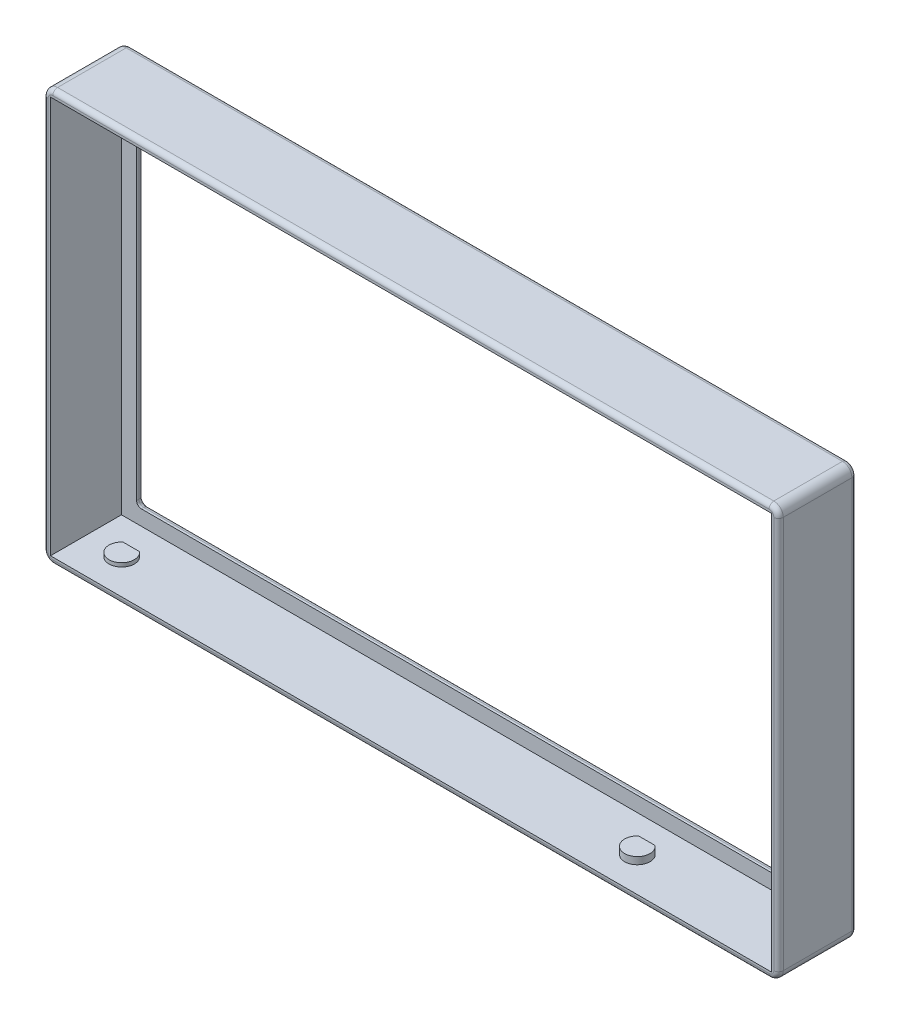
SolidWorks part; units mm, degrees
ref_plane "Front Plane" through (0, 0, 0) normal (0, 0, 1) x (1, 0, 0)
ref_plane "Top Plane" through (0, 0, 0) normal (0, 1, 0) x (1, 0, 0)
ref_plane "Right Plane" through (0, 0, 0) normal (1, 0, 0) x (0, 0, -1)
ref_plane "Plane1" through (0, 0, -28.2226) normal (0, 0, -1) x (-1, 0, 0)
sketch "Sketch1" plane through (0, 0, -28.2226) normal (0, 0, -1) x (-1, 0, 0)
  line L0 (-140.2742, 14.7559) -> (12.1258, 14.7559)
  line L1 (12.1258, 14.7559) -> (12.1258, 98.7359)
  line L2 (12.1258, 98.7359) -> (-140.2742, 98.7359)
  line L3 (-140.2742, 98.7359) -> (-140.2742, 14.7559)
  line L4 (-140.0742, 14.9559) -> (11.9258, 14.9559)
  line L5 (11.9258, 14.9559) -> (11.9258, 98.5359)
  line L6 (11.9258, 98.5359) -> (-140.0742, 98.5359)
  line L7 (-140.0742, 98.5359) -> (-140.0742, 14.9559)
  line L8 (-140.0742, 14.9559) -> (11.9258, 14.9559)
  line L9 (11.9258, 14.9559) -> (11.9258, 98.5359)
  line L10 (11.9258, 98.5359) -> (-140.0742, 98.5359)
  line L11 (-140.0742, 98.5359) -> (-140.0742, 14.9559)
  line L12 (13.6258, 13.2559) -> (13.6258, 100.2359)
  line L13 (13.6258, 100.2359) -> (-141.7742, 100.2359)
  line L14 (-141.7742, 100.2359) -> (-141.7742, 13.2559)
  line L15 (-141.7742, 13.2559) -> (13.6258, 13.2559)
  line L16 (-137.0742, 17.9559) -> (8.9258, 17.9559)
  line L17 (8.9258, 17.9559) -> (8.9258, 95.5359)
  line L18 (8.9258, 95.5359) -> (-137.0742, 95.5359)
  line L19 (-137.0742, 95.5359) -> (-137.0742, 17.9559)
  dimension "D1" = 0
  dimension "D2" = 0.2
  dimension "D3" = 1.5
  dimension "D4" = 3
extrude "Boss-Extrude2" add sketch "Sketch1" along normal blind 1.5 contours L14 L15 L12 L13 L3 L2 L1 L0 | L2 L3 L0 L1 L11 L10 L9 L8 | L10 L11 L8 L9 region at (140.1002, 56.7459, -28.2226) region at (138.3395, 56.7459, -28.2226) region at (64.0742, 13.434, -28.2226)
extrude "Boss-Extrude3" add sketch "Sketch1<4>" against normal blind 15 contours L14 L15 L12 L13 L3 L2 L1 L0 region at (64.0742, 13.434, -28.2226)
sketch "Sketch1<4>" plane through (0, 0, -28.2226) normal (0, 0, -1) x (-1, 0, 0) same geometry as "Sketch1"
fillet "Fillet1" radius 2 4 edges at (141.7742, 100.2359, -21.4726) (-13.6258, 100.2359, -21.4726) (-13.6258, 13.2559, -21.4726) (141.7742, 13.2559, -21.4726)
fillet "Fillet2" radius 1 16 edges at (-8.9258, 56.7459, -29.7226) (64.0742, 95.5359, -29.7226) (64.0742, 17.9559, -29.7226) (141.1884, 99.6501, -29.7226) (64.0742, 100.2359, -29.7226) (-13.04, 99.6501, -29.7226) (-13.6258, 56.7459, -29.7226) (-13.04, 13.8417, -29.7226) (64.0742, 13.2559, -29.7226) (141.1884, 13.8417, -29.7226) (141.7742, 56.7459, -29.7226) (137.0742, 56.7459, -29.7226) (137.0742, 95.5359, -28.9726) (137.0742, 17.9559, -28.9726) (-8.9258, 17.9559, -28.9726) (-8.9258, 95.5359, -28.9726)
fillet "Fillet3" radius 1 8 edges at (141.1884, 13.8417, -13.2226) (141.7742, 56.7459, -13.2226) (141.1884, 99.6501, -13.2226) (64.0742, 100.2359, -13.2226) (-13.04, 99.6501, -13.2226) (-13.6258, 56.7459, -13.2226) (-13.04, 13.8417, -13.2226) (64.0742, 13.2559, -13.2226)
sketch "Sketch2" plane through (0, 14.7559, 0) normal (0, 1, 0) x (1, 0, 0)
  line L0 (102.8242, 22.5958) -> (106.3242, 22.5958)
  line L1 (-6.1758, 22.5958) -> (-2.6758, 22.5958)
  circle A0 centre (-4.4258, 20.5726) radius 2.875 construction
  circle A1 centre (104.5742, 20.5726) radius 2.875 construction
  circle A2 centre (-4.4258, 20.5726) radius 2.875 construction
  circle A3 centre (104.5742, 20.5726) radius 2.875 construction
  circle A13 centre (-4.4258, 20.5726) radius 2.675
  circle A14 centre (104.5742, 20.5726) radius 2.675
  dimension "D2" = 3.5
  dimension "D3" = 3.5
  dimension "D1" = 0.2
extrude "Boss-Extrude4" add sketch "Sketch2" along normal blind 0.8 contours L1 A13 | L0 A14 region at (104.5742, 14.7559, -20.4018) region at (-4.4258, 14.7559, -20.4018)
sketch "Sketch4" plane through (0, 98.7359, 0) normal (0, -1, 0) x (1, 0, 0)
  line L0 (130.8242, -22.5958) -> (134.3242, -22.5958)
  line L1 (-6.1758, -22.5958) -> (-2.6758, -22.5958)
  circle A0 centre (132.5742, -20.5726) radius 2.875 construction
  circle A1 centre (-4.4258, -20.5726) radius 2.875 construction
  circle A2 centre (132.5742, -20.5726) radius 2.875 construction
  circle A3 centre (-4.4258, -20.5726) radius 2.875 construction
  circle A4 centre (-4.4258, -20.5726) radius 2.675
  circle A5 centre (132.5742, -20.5726) radius 2.675
  dimension "D2" = 3.5
  dimension "D3" = 3.5
  dimension "D1" = 0.2
extrude "Boss-Extrude5" add sketch "Sketch4" along normal blind 1 contours L0 A5 | L1 A4 region at (132.5742, 98.7359, -20.4018) region at (-4.4258, 98.7359, -20.4018)
extrude "Boss-Extrude6" add sketch "Sketch2<3>" along normal blind 1.5 contours L0 A14 region at (104.5742, 14.7559, -20.4018)
sketch "Sketch2<3>" plane through (0, 14.7559, 0) normal (0, 1, 0) x (1, 0, 0) same geometry as "Sketch2"
